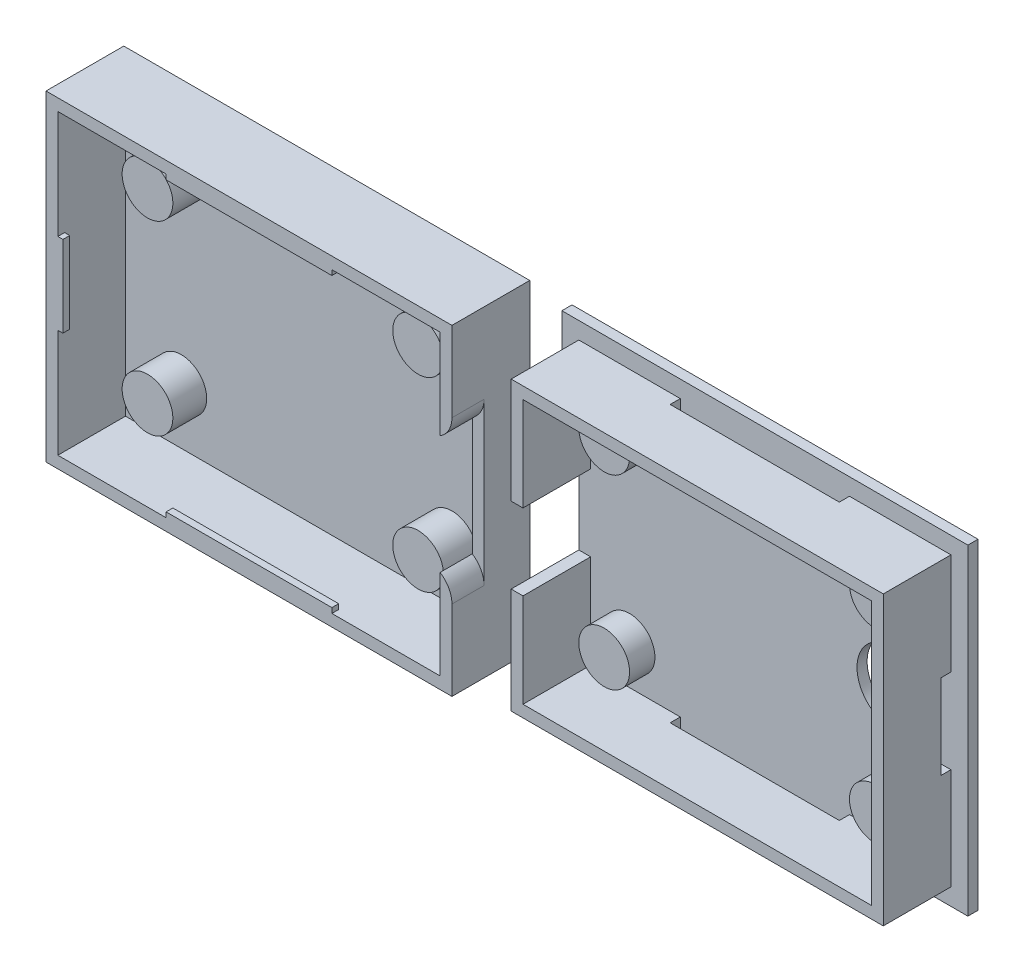
SolidWorks part; units mm, degrees
ref_plane "Alzado" through (0, 0, 0) normal (0, 0, 1) x (1, 0, 0)
ref_plane "Planta" through (0, 0, 0) normal (0, 1, 0) x (1, 0, 0)
ref_plane "Vista lateral" through (0, 0, 0) normal (1, 0, 0) x (0, 0, -1)
sketch "Croquis1" plane through (0, 0, 0) normal (0, 0, 1) x (1, 0, 0)
  line L0 (24, -19) -> (24, 19)
  line L1 (-24, 19) -> (24, 19)
  line L2 (-24, 19) -> (-24, -19)
  line L3 (-24, -19) -> (24, -19)
  line L5 (-24, 19) -> (24, -19) construction
  line L6 (-24, -19) -> (24, 19) construction
  line L7 (-20, 15) -> (20, 15) construction
  line L8 (-20, 15) -> (-20, -15) construction
  line L9 (-20, -15) -> (20, -15) construction
  line L10 (20, 15) -> (20, -15) construction
  line L11 (-20, 15) -> (20, -15) construction
  line L12 (-20, -15) -> (20, 15) construction
  line L13 (-77, 19) -> (-29, 19)
  line L14 (-77, 19) -> (-77, -19)
  line L15 (-77, -19) -> (-29, -19)
  line L16 (-29, 19) -> (-29, -19)
  line L17 (-77, 19) -> (-29, -19) construction
  line L18 (-77, -19) -> (-29, 19) construction
  circle A0 centre (15.1396, -0.0718) radius 4.25
  point P0 (0, 0)
  point P6 (0, 0)
  point P13 (-53, 0)
  dimension "D7" = 8.5
  dimension "D1" = 48
  dimension "D2" = 30
  dimension "D3" = 38
  dimension "D4" = 40
  dimension "D5" = 35.1396
  dimension "D6" = 14.9282
  dimension "D8" = 5
extrude "Saliente-Extruir1" add sketch "Croquis1" along normal blind 1.2
sketch "Croquis2" plane through (0, 0, 1.2) normal (0, 0, 1) x (1, 0, 0)
  line L0 (-26.5, 19) -> (-26.5, -19) construction
  line L1 (-29, 19) -> (-24, 19) construction
  line L4 (20.6, 15.6) -> (-20.6, 15.6)
  line L5 (-20.6, 15.6) -> (-20.6, 4.5)
  line L6 (-20.6, -15.6) -> (20.6, -15.6)
  line L7 (20.6, -15.6) -> (20.6, 15.6)
  line L8 (-22, -17) -> (22, -17)
  line L9 (22, -17) -> (22, 17)
  line L10 (22, 17) -> (-22, 17)
  line L11 (-22, 17) -> (-22, -17)
  line L12 (-22, -17) -> (22, -17)
  line L13 (22, -17) -> (22, 17)
  line L14 (22, 17) -> (-22, 17)
  line L15 (-22, 17) -> (-22, 4.5)
  line L16 (-22, 4.5) -> (-20.6, 4.5)
  line L17 (-22, -4.5) -> (-20.6, -4.5)
  line L18 (-22, -4.5) -> (-22, -17)
  line L19 (-22, 17) -> (-22, -17) construction
  line L20 (-20.6, -4.5) -> (-20.6, -15.6)
  line L21 (-20.6, 15.6) -> (-20.6, -15.6) construction
  line L22 (-20, 15) -> (20, 15) construction
  line L24 (-20, 15) -> (-20, -15) construction
  line L25 (20, 15) -> (20, -15) construction
  line L26 (-20, -15) -> (20, -15) construction
  line L31 (-29, -19) -> (-29, 19)
  line L32 (-29, 19) -> (-77, 19)
  line L33 (-77, 19) -> (-77, -19)
  line L34 (-77, -19) -> (-29, -19)
  line L35 (-29, -19) -> (-29, -7)
  line L36 (-29, 19) -> (-77, 19)
  line L37 (-77, 19) -> (-77, -19)
  line L38 (-77, -19) -> (-29, -19)
  line L41 (-30.4, 6.9982) -> (-30.4, 17.6)
  line L42 (-29, 7) -> (-29, 19)
  line L43 (-30.4, -17.6) -> (-30.4, 17.6)
  line L44 (-30.4, 17.6) -> (-75.6, 17.6)
  line L45 (-75.6, 17.6) -> (-75.6, -17.6)
  line L46 (-75.6, -17.6) -> (-30.4, -17.6)
  line L47 (-30.4, -17.6) -> (-30.4, -7.0018)
  line L48 (-30.4, 17.6) -> (-75.6, 17.6)
  line L49 (-75.6, 17.6) -> (-75.6, -17.6)
  line L50 (-75.6, -17.6) -> (-30.4, -17.6)
  line L51 (-29, 7) -> (-29, -7)
  line L52 (-30.4, 6.9982) -> (-30.4, -7.0018)
  circle A0 centre (-16, 11) radius 3
  circle A1 centre (16, 11) radius 3
  circle A2 centre (-16, -11) radius 3
  circle A3 centre (16, -11) radius 3
  circle A4 centre (-69, 11) radius 3
  circle A5 centre (-69, -11) radius 3
  circle A6 centre (-37, -11) radius 3
  circle A7 centre (-37, 11) radius 3
  dimension "D5" = 6
  dimension "D3" = 4.5
  dimension "D4" = 4.5
  dimension "D6" = 4
  dimension "D7" = 4
  dimension "D8" = 4
  dimension "D9" = 4
  dimension "D10" = 0
  dimension "D1" = 2
  dimension "D2" = 1.4
  dimension "D11" = 1.4
extrude "Saliente-Extruir2" add sketch "Croquis2" along normal blind 8 contours L51 L42 L36 L37 L38 L35 L41 L52 L47 L50 L49 L48 | A6 | A5 | A4 | A7 | A0 | A2 | A3 | A1 | L14 L15 L16 L5 L4 L7 L6 L20 L17 L18 L12 L13 region at (-53, -18.3878, 1.2) region at (-16, 11, 1.2) region at (16, 11, 1.2) region at (-16, -11, 1.2) region at (16, -11, 1.2) region at (-69, 11, 1.2) region at (-69, -11, 1.2) region at (-37, -11, 1.2) region at (-37, 11, 1.2)
sketch "Croquis3" plane through (0, -17, 0) normal (0, -1, 0) x (1, 0, 0)
  line L0 (-10, 1.2) -> (-10, 2.4)
  line L1 (-24, 1.2) -> (24, 1.2) construction
  line L2 (-10, 2.4) -> (10, 2.4)
  line L3 (10, 2.4) -> (10, 1.2)
  line L4 (-22, 1.2) -> (22, 1.2) construction
  line L5 (10, 1.2) -> (-10, 1.2)
  point P4 (0, 2.4)
  dimension "D1" = 20
  dimension "D2" = 1.2
extrude "Cortar-Extruir1" cut sketch "Croquis3" against normal up to surface (34 mm away) up to face at (0, 17, 5.2)
sketch "Croquis4" plane through (0, 0, 9.2) normal (0, 0, 1) x (1, 0, 0)
  circle A5 centre (16, -11) radius 3
  circle A6 centre (-16, -11) radius 3
  circle A7 centre (-16, 11) radius 3
  circle A8 centre (16, 11) radius 3
  circle A9 centre (16, 11) radius 3
  dimension "D1" = 0
extrude "Cortar-Extruir2" cut sketch "Croquis4" against normal blind 5
sketch "Croquis7" plane through (0, 0, 9.2) normal (0, 0, 1) x (1, 0, 0)
  line L0 (-30.4, 7) -> (-29, 7)
  line L3 (-30.4, -17.6) -> (-30.4, 17.6) construction
  line L4 (-29, 19) -> (-29, -19) construction
  line L6 (-29, 7) -> (-29, -7)
  line L7 (-29, -7) -> (-30.4, -7)
  line L8 (-30.4, -7) -> (-30.4, 7)
  point P6 (-29, 0)
  dimension "D1" = 14
extrude "Cortar-Extruir3" cut sketch "Croquis7" against normal blind 3.8
sketch "Croquis8" plane through (22, 0, 0) normal (1, 0, 0) x (0, 0, -1)
  line L0 (-1.2, 5) -> (-1.2, -5)
  line L1 (-1.2, -19) -> (-1.2, 19) construction
  line L2 (-1.2, -17) -> (-1.2, 17) construction
  line L3 (-1.2, -5) -> (-2.4, -5)
  line L4 (-2.4, -5) -> (-2.4, 5)
  line L5 (-2.4, 5) -> (-1.2, 5)
  point P6 (-1.2, 0)
  dimension "D1" = 10
  dimension "D2" = 1.2
extrude "Cortar-Extruir4" cut sketch "Croquis8" against normal up to next
sketch "Croquis9" plane through (0, 0, 9.2) normal (0, 0, 1) x (1, 0, 0)
  line L0 (-75.6, 4.8) -> (-75, 4.8)
  line L2 (-75.6, 17.6) -> (-75.6, -17.6) construction
  line L3 (-75, 4.8) -> (-75, -4.8)
  line L5 (-75, -4.8) -> (-75.6, -4.8)
  line L6 (-62.8, -17.6) -> (-62.8, -17)
  line L8 (-62.8, -17) -> (-43.2, -17)
  line L9 (-43.2, -17) -> (-43.2, -17.6)
  line L10 (-75.6, -17.6) -> (-30.4, -17.6) construction
  line L11 (-75.6, 17.6) -> (-75.6, -17.6) construction
  line L14 (-62.8, -17.6) -> (-43.2, -17.6)
  line L15 (-62.8, 17.6) -> (-62.8, 17)
  line L16 (-30.4, 17.6) -> (-75.6, 17.6) construction
  line L17 (-62.8, 17) -> (-43.2, 17)
  line L18 (-43.2, 17) -> (-43.2, 17.6)
  line L19 (-75.6, -17.6) -> (-30.4, -17.6) construction
  line L20 (-75.6, 4.8) -> (-75.6, -4.8)
  line L21 (-30.4, 17.6) -> (-75.6, 17.6) construction
  line L22 (-43.2, 17.6) -> (-62.8, 17.6)
  line L23 (-29, 19) -> (-77, 19) construction
  point P4 (-75, 0)
  point P14 (-53, -17.6)
  point P19 (-53, -17)
  point P24 (-53, 17)
  point P30 (-53, 19)
  dimension "D1" = 0.6
  dimension "D2" = 9.6
  dimension "D3" = 0.6
  dimension "D4" = 19.6
  dimension "D5" = 0.6
  dimension "D6" = 19.6
extrude "Saliente-Extruir3" add sketch "Croquis9" against normal blind 0.8
sketch "Croquis11" plane through (0, 0, 9.2) normal (0, 0, 1) x (1, 0, 0)
  circle A0 centre (-37, -11) radius 3 construction
  circle A1 centre (-37, 11) radius 3 construction
  circle A2 centre (-69, 11) radius 3 construction
  circle A3 centre (-69, -11) radius 3 construction
  circle A4 centre (-37, -11) radius 3
  circle A5 centre (-37, 11) radius 3
  circle A6 centre (-69, 11) radius 3
  circle A7 centre (-69, -11) radius 3
extrude "Cortar-Extruir5" cut sketch "Croquis11" against normal blind 4
sketch "Croquis12" plane through (0, 0, 1.2) normal (0, 0, 1) x (1, 0, 0)
  line L0 (-22, -7) -> (-22, 7)
  line L1 (-22, -4.5) -> (-22, -17) construction
  line L2 (-22, 17) -> (-22, 4.5) construction
  line L3 (-22, -7) -> (-24, -7)
  line L4 (-24, 19) -> (-24, -19) construction
  line L5 (-24, -7) -> (-24, 7)
  line L6 (-24, 7) -> (-22, 7)
  point P6 (-22, 0)
  dimension "D1" = 14
extrude "Cortar-Extruir6" cut sketch "Croquis12" against normal up to next
fillet "Redondeo1" radius 3 2 edges at (-29, -7, 7.3) (-29, 7, 7.3)
fillet "Redondeo2" radius 3 2 edges at (-24, -7, 0.6) (-24, 7, 0.6)
